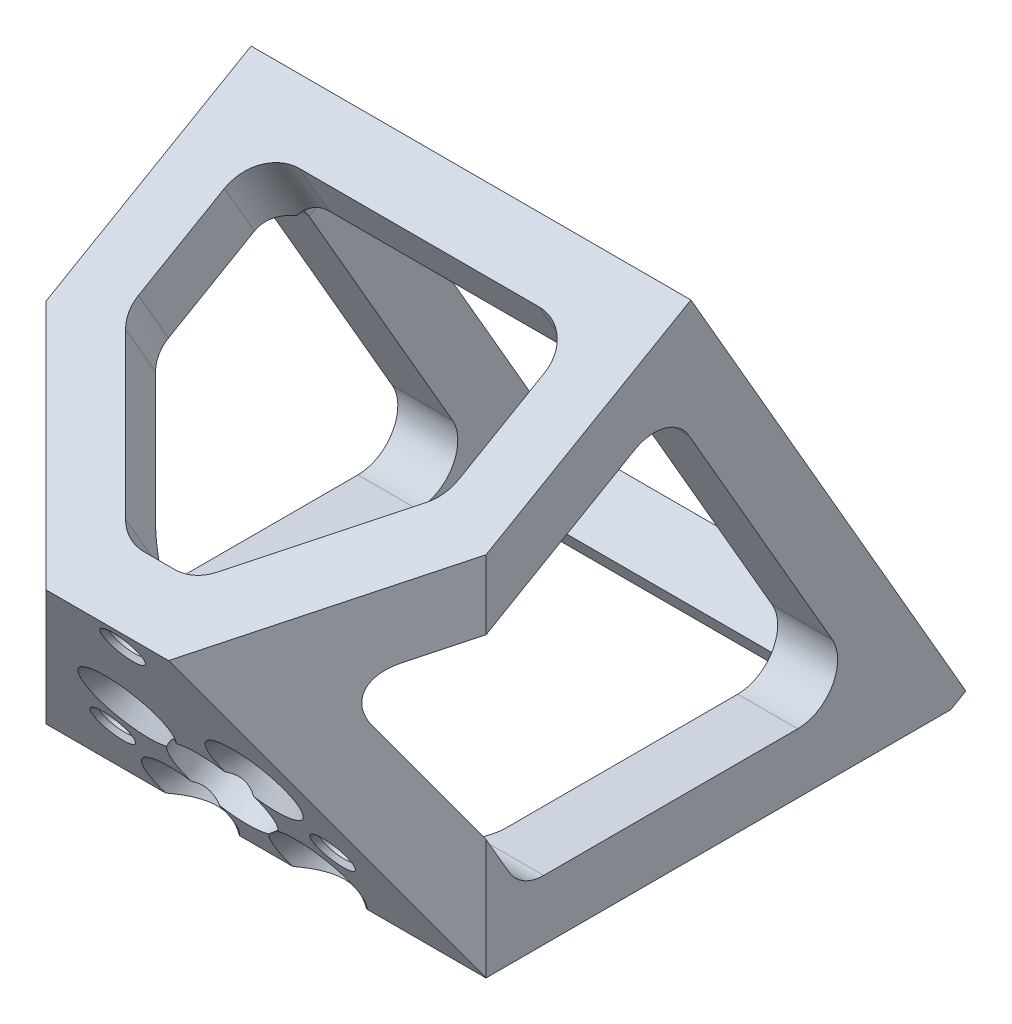
SolidWorks part; units mm, degrees
ref_plane "Front Plane" through (0, 0, 0) normal (0, 0, 1) x (1, 0, 0)
ref_plane "Top Plane" through (0, 0, 0) normal (0, 1, 0) x (1, 0, 0)
ref_plane "Right Plane" through (0, 0, 0) normal (1, 0, 0) x (0, 0, -1)
sketch "Sketch1" plane through (0, 0, 0) normal (1, 0, 0) x (0, 0, -1)
  line L0 (0, 0) -> (24.2487, 0)
  line L1 (24.2487, 0) -> (10.2487, 24.2487)
  line L2 (10.2487, 24.2487) -> (-7.9378, 13.7487)
  line L3 (-7.9378, 13.7487) -> (0, 0)
  dimension "D1" = 28
  dimension "D2" = 24.2487
  dimension "D3" = 60
  dimension "D4" = 21
extrude "Boss-Extrude1" add sketch "Sketch1" along normal blind 22
sketch "Sketch2" plane through (22, 0, 0) normal (1, 0, 0) x (0, 0, -1)
  line L0 (-3.8397, 12.6506) -> (1.7321, 3)
  line L1 (1.7321, 3) -> (19.0526, 3)
  line L2 (19.0526, 3) -> (9.1506, 20.1506)
  line L3 (9.1506, 20.1506) -> (-3.8397, 12.6506)
  line L4 (-7.9378, 13.7487) -> (0, 0)
  line L5 (0, 0) -> (24.2487, 0)
  line L6 (24.2487, 0) -> (10.2487, 24.2487)
  line L7 (10.2487, 24.2487) -> (-7.9378, 13.7487)
  line L8 (-7.9378, 13.7487) -> (0, 0) construction
  line L9 (0, 0) -> (24.2487, 0) construction
  line L10 (24.2487, 0) -> (10.2487, 24.2487) construction
  line L11 (10.2487, 24.2487) -> (-7.9378, 13.7487) construction
  dimension "D2" = 3
extrude "Cut-Extrude1" cut sketch "Sketch2" against normal through all both and the other way through all
sketch "Sketch12" plane through (0, 0, 0) normal (0, -1, 0) x (1, 0, 0)
  line L0 (22, 0) -> (11, 11)
  line L1 (11, 11) -> (0, 0)
  line L3 (22, 0) -> (22, 20.987)
  line L4 (22, 20.987) -> (0, 20.987)
  line L5 (0, 20.987) -> (0, 0)
extrude "Cut-Extrude5" cut sketch "Sketch12" against normal through all both and the other way through all
sketch "Sketch3" plane through (0, 10.5, -18.1865) normal (0, 0.5, -0.866) x (-1, 0, 0)
  line L0 (-19, 12.8756) -> (-19, -9.1244)
  line L1 (-19, -9.1244) -> (-3, -9.1244)
  line L2 (-3, -9.1244) -> (-3, 12.8756)
  line L3 (-3, 12.8756) -> (-19, 12.8756)
  line L4 (0, -12.1244) -> (0, 15.8756)
  line L5 (0, 15.8756) -> (-22, 15.8756)
  line L6 (-22, 15.8756) -> (-22, -12.1244)
  line L7 (-22, -12.1244) -> (0, -12.1244)
  line L8 (0, -12.1244) -> (0, 15.8756) construction
  line L9 (0, 15.8756) -> (-22, 15.8756) construction
  line L10 (-22, 15.8756) -> (-22, -12.1244) construction
  line L11 (-22, -12.1244) -> (0, -12.1244) construction
  dimension "D2" = 3
extrude "Cut-Extrude2" cut sketch "Sketch3" against normal up to surface (18 mm away) up to face at (11, 7.2169, 0.7026)
fillet "Fillet1" radius 2 7 edges at (1.5, 20.1506, -9.1506) (20.5, 20.1506, -9.1506) (1.5, 3, -19.0526) (20.5, 3, -19.0526) (20.5, 3, -1.7321) (1.5, 3, -1.7321) (11, 12.6506, 3.8397)
sketch "Sketch4" plane through (0, 13.7487, 7.9378) normal (0, 0.866, 0.5) x (1, 0, 0)
  line L8 (3, 18) -> (3, 10.2843)
  line L9 (9.3084, 3) -> (12.6916, 3)
  line L10 (19, 10.2843) -> (19, 18)
  line L11 (19, 18) -> (3, 18)
  line L12 (3, 18) -> (3, 10.2843)
  line L13 (9.3084, 3) -> (12.6916, 3)
  line L14 (19, 10.2843) -> (19, 18)
  line L15 (19, 18) -> (3, 18)
  line L18 (12.6916, 3) -> (19, 10.2843)
  line L19 (12.6916, 3) -> (19, 10.2843)
  line L20 (3, 10.2843) -> (9.3084, 3)
  line L21 (3, 10.2843) -> (9.3084, 3)
  dimension "D1" = 3
extrude "Cut-Extrude3" cut sketch "Sketch4" against normal through all
fillet "Fillet5" radius 2 8 edges at (19, 2, -2.3094) (3, 2, -2.3094) (19, 21.4497, -8.4006) (3, 21.4497, -8.4006) (19, 17.5918, -1.7186) (3, 17.5918, -1.7186) (9.3084, 13.0836, 4.0897) (12.6916, 13.0836, 4.0897)
fillet "Fillet6" radius 2 4 edges at (19, 1.8481, -21.4497) (3, 1.8481, -21.4497) (3, 20.4006, -9.5836) (19, 20.4006, -9.5836)
fillet "Fillet7" radius 2 2 edges at (3, 1.4151, -19.9676) (19, 1.4151, -19.9676)
chamfer "Chamfer1" distance 1 angle 30 1 edges at (11, 0, -24.2487) first distance on face at (11, 0, -12.1244)
hole_wizard "M2x0.4 Tapped Hole1" positions "Sketch6" profile "Sketch7" tap size "M2x0.4" standard "ANSI Metric"
sketch "Sketch6" plane through (0, 10.5, -18.1865) normal (0, 0.5, -0.866) x (-1, 0, 0)
  line L1 (-19, 12.8756) -> (-22, 12.8756) construction
  line L2 (-19, 15.8756) -> (-19, 12.8756) construction
  line L3 (-19, 15.8756) -> (-19, 12.8756) construction
  line L4 (-22, -11.6244) -> (0, -11.6244) construction
  line L5 (-11, 15.8756) -> (-11, -11.6244) construction
  line L6 (-22, 15.8756) -> (0, 15.8756) construction
  line L7 (-19, 12.8756) -> (-22, 12.8756) construction
  line L8 (-22, -11.6244) -> (-22, 15.8756) construction
  point P0 (-20.5, 14.3756)
  point P7 (-20.5, -6.6244)
  point P12 (-20.5, 12.8756)
  point P13 (-19, 14.3756)
  point P24 (-1.5, -6.6244)
  point P25 (-1.5, 14.3756)
  dimension "D1" = 5
cosmetic thread "Hole Thread1" parameters "D1"=2.4, "D2"=2
cosmetic thread "Hole Thread2" parameters "D1"=2.4, "D2"=2
cosmetic thread "Hole Thread3" parameters "D1"=2.4, "D2"=2
cosmetic thread "Hole Thread4" parameters "D1"=2.4, "D2"=2
sketch "Sketch7" plane through (20.5, 22.9497, -10.9987) normal (1, 0, 0) x (0, 0.866, 0.5)
  line L0 (0, 0) -> (0, 4.0807)
  line L1 (0, 4.0807) -> (0.8, 3.6)
  line L2 (0.8, 3.6) -> (0.8, 0)
  line L5 (0.8, 0) -> (0, 0)
  line L10 (0, 4.0807) -> (-0.8, 3.6) construction
  line L11 (0, -6.35) -> (0, 107.95) construction
  dimension "Tap Drill Dia." = 1.6
  dimension "Tap Drill Depth" = 3.6
  dimension "Drill Angle" = 118
hole_wizard "Ø5.0mm Dowel Hole1" positions "Sketch8" profile "Sketch9" hole size "Ø5.0" standard "ANSI Metric"
sketch "Sketch8" plane through (0, 0, 0) normal (0, -0.5, 0.866) x (1, 0, 0)
  line L0 (17, 10.8756) -> (5, -7.1244) construction
  arc A0 (19, 10.8756) -> (17, 12.8756) centre (17, 10.8756) ccw construction
  arc A1 (3, -7.1244) -> (5, -9.1244) centre (5, -7.1244) ccw construction
  point P0 (11, 4.3756)
  point P25 (11, 1.8756)
  dimension "D1" = 2.5
sketch "Sketch9" plane through (11, 3.7894, 2.1878) normal (1, 0, 0) x (0, -0.866, -0.5)
  line L0 (0, 0) -> (0, 19.5012)
  line L1 (0, 19.5012) -> (2.5, 17.999)
  line L2 (2.5, 17.999) -> (2.5, 0)
  line L5 (2.5, 0) -> (0, 0)
  line L10 (0, 19.5012) -> (-2.5, 17.999) construction
  line L11 (0, -6.35) -> (0, 107.95) construction
  dimension "Hole Dia." = 5
  dimension "Hole Depth" = 17.999
  dimension "Drill Angle" = 118
hole_wizard "CSK for M2 Flat Head Machine Screw1" positions "Sketch10" profile "Sketch11" countersink size "M2" standard "ANSI Metric"
sketch "Sketch10" plane through (0, 0, 0) normal (0, -0.5, 0.866) x (1, 0, 0)
  line L1 (7.818, 7.5576) -> (14.182, 7.5576)
  line L2 (7.818, 7.5576) -> (7.818, 1.1937)
  line L3 (7.818, 1.1937) -> (14.182, 1.1937)
  line L4 (14.182, 7.5576) -> (14.182, 1.1937)
  line L5 (7.818, 7.5576) -> (14.182, 1.1937) construction
  circle A0 centre (11, 4.3756) radius 2.5 construction
  point P0 (7.818, 7.5576)
  point P2 (14.182, 7.5576)
  point P4 (14.182, 1.1937)
  point P6 (7.818, 1.1937)
  point P112 (11, 4.3756)
  dimension "D1" = 9
sketch "Sketch11" plane through (7.818, 6.5451, 3.7788) normal (1, 0, 0) x (0, -0.866, -0.5)
  line L0 (0, 0) -> (0, 5.721)
  line L1 (0, 5.721) -> (1.2, 5)
  line L2 (1.2, 5) -> (1.2, 1)
  line L3 (1.2, 1) -> (2.2, 0)
  line L5 (2.2, 0) -> (0, 0)
  line L6 (-1.2, 1) -> (-2.2, 0) construction
  line L10 (0, 5.721) -> (-1.2, 5) construction
  line L11 (0, -6.35) -> (0, 107.95) construction
  dimension "Hole Dia." = 2.4
  dimension "Hole Depth" = 5
  dimension "Near C'Sink Dia." = 4.4
  dimension "Near C'Sink Angle" = 90
  dimension "Drill Angle" = 118
hole_wizard "M2x0.4 Tapped Hole2" positions "Sketch13" profile "Sketch14" tap size "M2x0.4" standard "ANSI Metric"
sketch "Sketch13" plane through (0, 0, 0) normal (0, -0.5, 0.866) x (1, 0, 0)
  line L0 (5.5, 4.35) -> (16.5, 4.35) construction
  line L2 (11, 14.35) -> (11, 4.35) construction
  line L4 (14.0622, 15.8756) -> (7.9378, 15.8756) construction
  line L5 (5.97, 0) -> (0, 0) construction
  point P0 (11, 14.35)
  point P3 (5.5, 4.35)
  point P6 (16.5, 4.35)
  point P20 (11, 15.8756)
  dimension "D1" = 4.35
  dimension "D2" = 11
  dimension "D3" = 10
sketch "Sketch14" plane through (11, 12.4275, 7.175) normal (1, 0, 0) x (0, -0.866, -0.5)
  line L0 (0, 0) -> (0, 5.6807)
  line L1 (0, 5.6807) -> (0.8, 5.2)
  line L2 (0.8, 5.2) -> (0.8, 0.225)
  line L3 (0.8, 0.225) -> (1.025, 0)
  line L5 (1.025, 0) -> (0, 0)
  line L6 (-0.8, 0.225) -> (-1.025, 0) construction
  line L10 (0, 5.6807) -> (-0.8, 5.2) construction
  line L11 (0, -6.35) -> (0, 107.95) construction
  dimension "Tap Drill Dia." = 1.6
  dimension "Tap Drill Depth" = 5.2
  dimension "Near C'Sink Dia." = 2.05
  dimension "Near C'Sink Angle" = 90
  dimension "Drill Angle" = 118
cosmetic thread "Hole Thread5" parameters "D1"=3, "D2"=2
cosmetic thread "Hole Thread6" parameters "D1"=3, "D2"=2
cosmetic thread "Hole Thread7" parameters "D1"=3.0001, "D2"=2
equation "\"strutWidth\"= 3mm"
equation "\"D2@Sketch2\"=\"strutWidth\""
equation "\"D2@Sketch3\"=\"strutWidth\""
equation "\"D1@Sketch4\"=\"strutWidth\""
equation "\"cutterRadius\"= 2mm"
equation "\"D1@Fillet1\"=\"cutterRadius\""
equation "\"D1@Fillet5\"=\"cutterRadius\""
equation "\"D1@Fillet6\"=\"cutterRadius\""
equation "\"D1@Fillet7\"=\"cutterRadius\""
